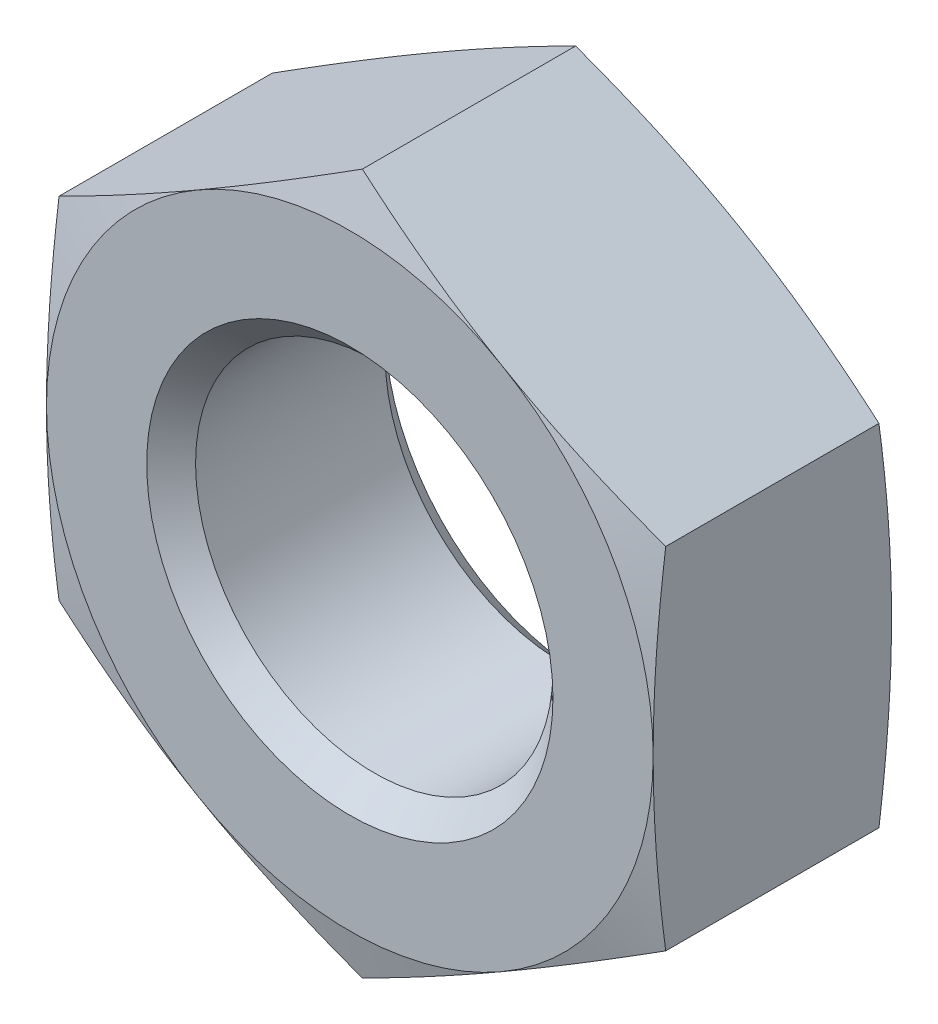
SolidWorks part; units mm, degrees
material "Cast Alloy Steel"
ref_plane "Front Plane" through (0, 0, 0) normal (0, 0, 1) x (1, 0, 0)
ref_plane "Top Plane" through (0, 0, 0) normal (0, 1, 0) x (1, 0, 0)
ref_plane "Right Plane" through (0, 0, 0) normal (1, 0, 0) x (0, 0, -1)
sketch "Sketch1" plane through (0, 0, 0) normal (1, 0, 0) x (0, 0, -1)
  line L0 (0, 0) -> (0, 7.112)
  line L1 (0, 7.112) -> (0.3811, 8.5344)
  line L2 (0.3811, 8.5344) -> (5.2069, 8.5344)
  line L3 (5.2069, 8.5344) -> (5.588, 7.112)
  line L4 (5.588, 7.112) -> (5.588, 0)
  line L5 (5.588, 0) -> (0, 0)
  line L6 (5.588, 0) -> (0, 0) construction
sketch "Sketch2" plane through (0, 0, 0) normal (0, 0, 1) x (1, 0, 0)
  line L0 (-14.224, 14.224) -> (-14.224, -14.224)
  line L1 (-14.224, -14.224) -> (14.224, -14.224)
  line L2 (14.224, -14.224) -> (14.224, 14.224)
  line L3 (14.224, 14.224) -> (-14.224, 14.224)
  line L4 (-7.112, 4.1061) -> (-7.112, -4.1061)
  line L5 (-7.112, -4.1061) -> (0, -8.2122)
  line L6 (0, -8.2122) -> (7.112, -4.1061)
  line L7 (7.112, -4.1061) -> (7.112, 4.1061)
  line L8 (7.112, 4.1061) -> (0, 8.2122)
  line L9 (0, 8.2122) -> (-7.112, 4.1061)
revolve "Revolve1" add sketch "Sketch1" angle 360 about L6 reverse direction yes
extrude "Cut-Extrude1" cut sketch "Sketch2" against normal blind 5.588
sketch "Sketch3" plane through (0, 0, 0) normal (1, 0, 0) x (0, 0, -1)
  line L0 (0, 0) -> (0, 4.7625)
  line L1 (0, 4.7625) -> (0.5728, 4.1897)
  line L2 (0.5728, 4.1897) -> (5.0152, 4.1897)
  line L3 (5.0152, 4.1897) -> (5.588, 4.7625)
  line L4 (5.588, 4.7625) -> (5.588, 0)
  line L5 (5.588, 0) -> (0, 0)
  line L6 (5.588, 0) -> (0, 0) construction
revolve "Cut-Revolve1" cut sketch "Sketch3" angle 360 about L6 reverse direction yes
cosmetic thread "Cosmetic Thread1" parameters "D1"=5.588, "D2"=9.525
ref_plane "NUT XY" through (0, 0, 0) normal (0, 0, 1) x (1, 0, 0)
ref_plane "NUT XZ" through (0, 0, 0) normal (0, -1, 0) x (-1, 0, 0)
ref_plane "NUT YZ" through (0, 0, 0) normal (1, 0, 0) x (0, 0, -1)
ref_axis "NUT X" through (-80.9, 0, 0) along (1, 0, 0)
ref_axis "NUT Y" through (0, -50, 0) along (0, 1, 0)
ref_axis "NUT Z" through (0, 0, 80.9) along (0, 0, -1)
sketch3d "NUT"
  point P0 (0, 0, 0)
ref_plane "a1 XY" through (0, 0, 0) normal (0, 0, 1) x (1, 0, 0)
ref_plane "a1 XZ" through (0, 7.112, 0) normal (0, -1, 0) x (-1, 0, 0)
ref_plane "a1 YZ" through (-7.112, 0, 0) normal (1, 0, 0) x (0, 0, -1)
ref_axis "a1 X" through (-80.9, 7.112, 0) along (1, 0, 0)
ref_axis "a1 Y" through (-7.112, -50, 0) along (0, 1, 0)
ref_axis "a1 Z" through (-7.112, 7.112, 80.9) along (0, 0, -1)
sketch3d "a1"
  point P0 (-7.112, 7.112, 0)
ref_plane "a2 XY" through (0, 0, 0) normal (0, 0, 1) x (1, 0, 0)
ref_plane "a2 XZ" through (0, 7.112, 0) normal (0, -1, 0) x (-1, 0, 0)
ref_plane "a2 YZ" through (7.112, 0, 0) normal (1, 0, 0) x (0, 0, -1)
ref_axis "a2 X" through (-80.9, 7.112, 0) along (1, 0, 0)
ref_axis "a2 Y" through (7.112, -50, 0) along (0, 1, 0)
ref_axis "a2 Z" through (7.112, 7.112, 80.9) along (0, 0, -1)
sketch3d "a2"
  point P0 (7.112, 7.112, 0)
ref_plane "b1 XY" through (0, 0, 0) normal (1, 0, 0) x (0, 0, -1)
ref_plane "b1 XZ" through (0, 7.112, 0) normal (0, -1, 0) x (-1, 0, 0)
ref_plane "b1 YZ" through (0, 0, 0) normal (0, 0, -1) x (-1, 0, 0)
ref_axis "b1 X" through (0, 7.112, 80.9) along (0, 0, -1)
ref_axis "b1 Y" through (0, -50, 0) along (0, 1, 0)
ref_axis "b1 Z" through (80.9, 7.112, 0) along (-1, 0, 0)
sketch3d "b1"
  point P0 (0, 7.112, 0)
ref_plane "b2 XY" through (0, 0, 0) normal (1, 0, 0) x (0, 0, -1)
ref_plane "b2 XZ" through (0, 7.112, 0) normal (0, -1, 0) x (-1, 0, 0)
ref_plane "b2 YZ" through (0, 0, -5.588) normal (0, 0, -1) x (-1, 0, 0)
ref_axis "b2 X" through (0, 7.112, 80.9) along (0, 0, -1)
ref_axis "b2 Y" through (0, -50, -5.588) along (0, 1, 0)
ref_axis "b2 Z" through (80.9, 7.112, -5.588) along (-1, 0, 0)
sketch3d "b2"
  point P0 (0, 7.112, -5.588)
ref_plane "e XY" through (0, 0, 0) normal (1, 0, 0) x (0, 0, -1)
ref_plane "e XZ" through (0, 0, 0) normal (0, -1, 0) x (-1, 0, 0)
ref_plane "e YZ" through (0, 0, -5.588) normal (0, 0, -1) x (-1, 0, 0)
ref_axis "e X" through (0, 0, 80.9) along (0, 0, -1)
ref_axis "e Y" through (0, -50, -5.588) along (0, 1, 0)
ref_axis "e Z" through (80.9, 0, -5.588) along (-1, 0, 0)
sketch3d "e"
  point P0 (0, 0, -5.588)
ref_plane "ol1 XY" through (0, 0, 0) normal (0, 1, 0) x (1, 0, 0)
ref_plane "ol1 XZ" through (0, 0, -7.112) normal (0, 0, 1) x (1, 0, 0)
ref_plane "ol1 YZ" through (0, 0, 0) normal (1, 0, 0) x (0, 0, -1)
ref_axis "ol1 X" through (-80.9, 0, -7.112) along (1, 0, 0)
ref_axis "ol1 Y" through (0, 0, 50) along (0, 0, -1)
ref_axis "ol1 Z" through (0, 50, -7.112) along (0, -1, 0)
sketch3d "ol1"
  point P0 (0, 0, -7.112)
ref_plane "ol2 XY" through (0, 0, 0) normal (0, 1, 0) x (1, 0, 0)
ref_plane "ol2 XZ" through (0, 0, -7.112) normal (0, 0, 1) x (1, 0, 0)
ref_plane "ol2 YZ" through (5.588, 0, 0) normal (1, 0, 0) x (0, 0, -1)
ref_axis "ol2 X" through (-80.9, 0, -7.112) along (1, 0, 0)
ref_axis "ol2 Y" through (5.588, 0, 50) along (0, 0, -1)
ref_axis "ol2 Z" through (5.588, 50, -7.112) along (0, -1, 0)
sketch3d "ol2"
  point P0 (5.588, 0, -7.112)
ref_plane "th1 XY" through (0, 0, 0) normal (1, 0, 0) x (0, 0, -1)
ref_plane "th1 XZ" through (0, 4.7625, 0) normal (0, -1, 0) x (-1, 0, 0)
ref_plane "th1 YZ" through (0, 0, -5.588) normal (0, 0, -1) x (-1, 0, 0)
ref_axis "th1 X" through (0, 4.7625, 80.9) along (0, 0, -1)
ref_axis "th1 Y" through (0, -50, -5.588) along (0, 1, 0)
ref_axis "th1 Z" through (80.9, 4.7625, -5.588) along (-1, 0, 0)
sketch3d "th1"
  point P0 (0, 4.7625, -5.588)
ref_plane "th2 XY" through (0, 0, 0) normal (1, 0, 0) x (0, 0, -1)
ref_plane "th2 XZ" through (0, -4.7625, 0) normal (0, -1, 0) x (-1, 0, 0)
ref_plane "th2 YZ" through (0, 0, -5.588) normal (0, 0, -1) x (-1, 0, 0)
ref_axis "th2 X" through (0, -4.7625, 80.9) along (0, 0, -1)
ref_axis "th2 Y" through (0, -50, -5.588) along (0, 1, 0)
ref_axis "th2 Z" through (80.9, -4.7625, -5.588) along (-1, 0, 0)
sketch3d "th2"
  point P0 (0, -4.7625, -5.588)
